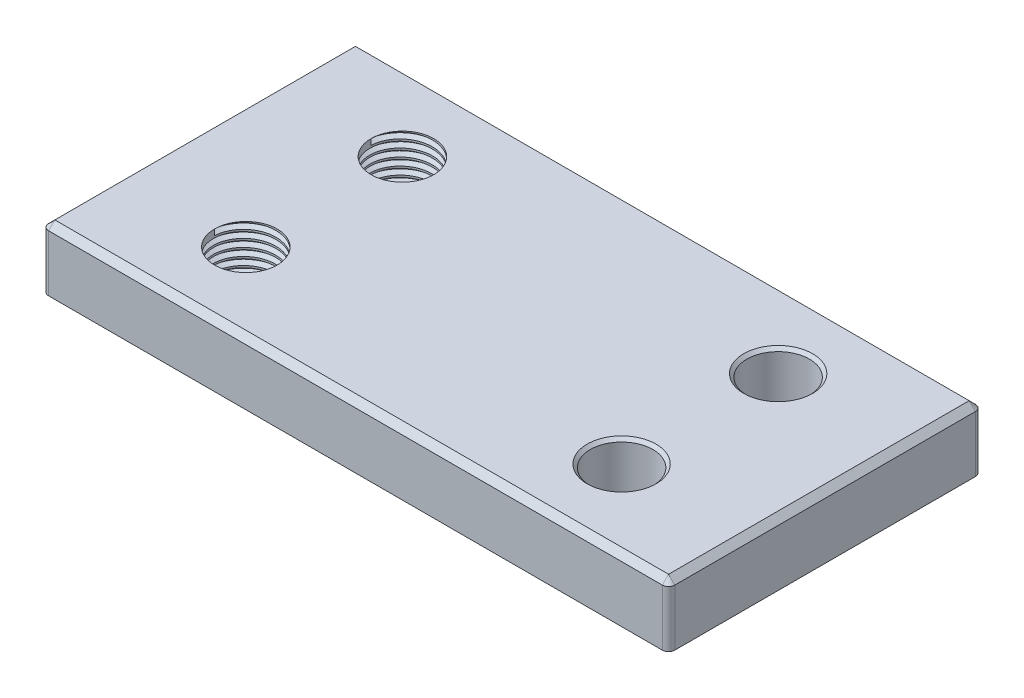
SolidWorks part; units mm, degrees
ref_plane "Front Plane" through (0, 0, 0) normal (0, 0, 1) x (1, 0, 0)
ref_plane "Top Plane" through (0, 0, 0) normal (0, 1, 0) x (1, 0, 0)
ref_plane "Right Plane" through (0, 0, 0) normal (1, 0, 0) x (0, 0, -1)
sketch "Sketch2" plane through (0, 0, 0) normal (0, 1, 0) x (1, 0, 0)
  line L0 (-50, 24) -> (-50, -24)
  line L1 (-49, -25) -> (49, -25)
  line L2 (50, -24) -> (50, 24)
  line L3 (49, 25) -> (-49, 25)
  line L4 (-50, 0) -> (50, 0) construction
  circle A1 centre (30, 12.5) radius 5
  circle A2 centre (30, -12.5) radius 5
  arc A4 (-50, -24) -> (-49, -25) centre (-49, -24) ccw
  arc A5 (49, -25) -> (50, -24) centre (49, -24) ccw
  arc A6 (50, 24) -> (49, 25) centre (49, 24) ccw
  arc A7 (-50, 24) -> (-49, 25) centre (-49, 24) cw
  circle A8 centre (-30, 12.5) radius 5
  circle A9 centre (-30, -12.5) radius 5
  point P3 (0, 25)
  point P5 (-50, 0)
  point P19 (-50, -25)
  point P22 (50, -25)
  point P25 (50, 25)
  dimension "D6" = 10
  dimension "D7" = 1
  dimension "D8" = 10
  dimension "D1" = 50
  dimension "D2" = 100
  dimension "D3" = 25
  dimension "D4" = 20
  dimension "D5" = 20
extrude "Boss-Extrude1" add sketch "Sketch2" along normal mid plane 10
chamfer "Chamfer1" distance 1 angle 45 8 edges at (0, 5, -25) (-49.7071, 5, -24.7071) (49.7071, 5, -24.7071) (-50, 5, 0) (50, 5, 0) (-49.7071, 5, 24.7071) (49.7071, 5, 24.7071) (0, 5, 25)
chamfer "Chamfer2" distance 0.5 angle 45 2 edges at (30, 5, -7.5) (30, 5, 7.5)
thread "Thread1" pitch 1.25 method cut profile "Thread Profile2" start angle 0, offset 0, length 10, pitch 1.25, diameter 10
ref_plane "Plane2" through (-35, 5, -12.5) normal (0, 0, 1) x (-1, 0, 0)
sketch "Thread Profile2" plane through (-35, 5, -12.5) normal (0, 0, 1) x (-1, 0, 0)
  line L0 (0, 0) -> (0, 1.25) construction
  line L1 (0, 0) -> (0.6766, 0.3906)
  line L2 (0.6766, 0.3906) -> (0.6766, 0.5469)
  line L3 (0.6766, 0.5469) -> (0, 0.9375)
  line L4 (0.6766, 0.4687) -> (0, 0.4687) construction
  line L11 (0, 0) -> (0, 0.9375)
  point P2 (0, 0)
  dimension "Pitch" = 1.25
  dimension "Profile_Angle" = 60
  dimension "Profile_Land" = 0.1562
  dimension "Profile_Height" = 0.6766
thread "Thread2" pitch 1.25 method cut profile "Thread Profile3" start angle 0, offset 0, length 10, pitch 1.25, diameter 10
ref_plane "Plane3" through (-35, 5, 12.5) normal (0, 0, 1) x (-1, 0, 0)
sketch "Thread Profile3" plane through (-35, 5, 12.5) normal (0, 0, 1) x (-1, 0, 0)
  line L0 (0, 0) -> (0, 1.25) construction
  line L1 (0, 0) -> (0.6766, 0.3906)
  line L2 (0.6766, 0.3906) -> (0.6766, 0.5469)
  line L3 (0.6766, 0.5469) -> (0, 0.9375)
  line L4 (0.6766, 0.4687) -> (0, 0.4687) construction
  line L11 (0, 0) -> (0, 0.9375)
  point P2 (0, 0)
  dimension "Pitch" = 1.25
  dimension "Profile_Angle" = 60
  dimension "Profile_Land" = 0.1562
  dimension "Profile_Height" = 0.6766
